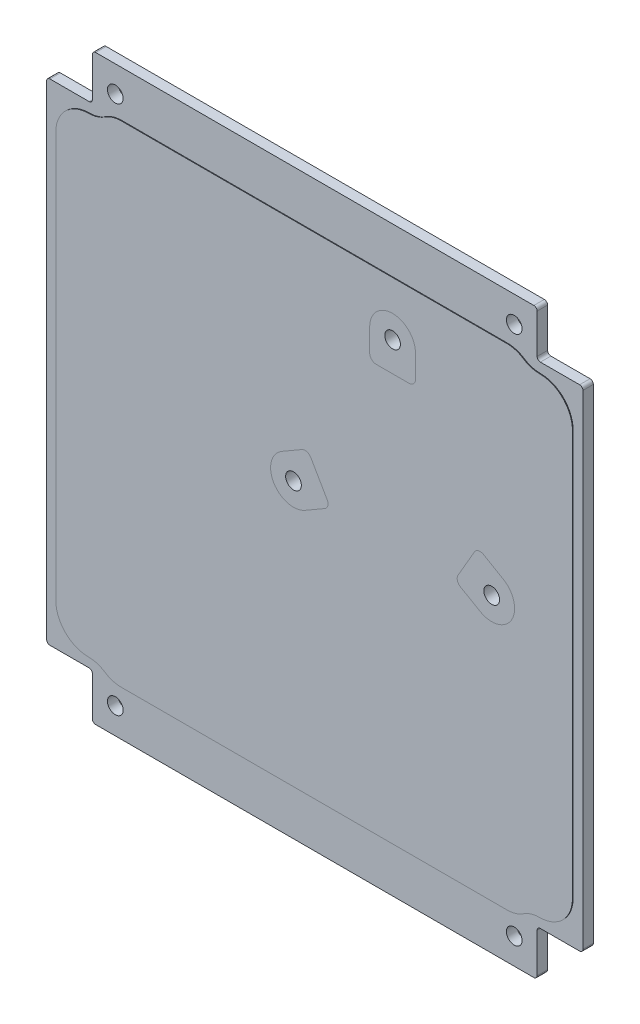
SolidWorks part; units mm, degrees
material "PET"
ref_plane "Front Plane" through (0, 0, 0) normal (0, 0, 1) x (1, 0, 0)
ref_plane "Top Plane" through (0, 0, 0) normal (0, 1, 0) x (1, 0, 0)
ref_plane "Right Plane" through (0, 0, 0) normal (1, 0, 0) x (0, 0, -1)
sketch "Sketch1" plane through (0, 0, 0) normal (0, 0, 1) x (1, 0, 0)
  line L0 (-34, 44) -> (-34, 38)
  line L1 (-33.5, -44.5) -> (33.5, -44.5)
  line L2 (-41, 37) -> (-41, -37)
  line L3 (-33.5, 44.5) -> (33.5, 44.5)
  line L4 (41, -37) -> (41, 37)
  line L5 (34, -44) -> (34, -38)
  line L6 (34.5, -37.5) -> (40.5, -37.5)
  line L7 (-34.5, 37.5) -> (-40.5, 37.5)
  line L8 (34, 44) -> (34, 38)
  line L9 (34.5, 37.5) -> (40.5, 37.5)
  line L10 (-40.5, -37.5) -> (-34.5, -37.5)
  line L11 (-34, -38) -> (-34, -44)
  line L12 (-34.5, -38) -> (34.5, 38) construction
  line L13 (34.5, -38) -> (-34.5, 38) construction
  arc A0 (-33.5, 44.5) -> (-34, 44) centre (-33.5, 44) ccw
  arc A1 (33.5, 44.5) -> (34, 44) centre (33.5, 44) cw
  arc A2 (34, 38) -> (34.5, 37.5) centre (34.5, 38) ccw
  arc A3 (40.5, 37.5) -> (41, 37) centre (40.5, 37) cw
  arc A4 (33.5, -44.5) -> (34, -44) centre (33.5, -44) ccw
  arc A5 (34.5, -37.5) -> (34, -38) centre (34.5, -38) ccw
  arc A6 (40.5, -37.5) -> (41, -37) centre (40.5, -37) ccw
  arc A7 (-34, -44) -> (-33.5, -44.5) centre (-33.5, -44) ccw
  arc A8 (-34, -38) -> (-34.5, -37.5) centre (-34.5, -38) ccw
  arc A9 (-41, -37) -> (-40.5, -37.5) centre (-40.5, -37) ccw
  arc A10 (-40.5, 37.5) -> (-41, 37) centre (-40.5, 37) ccw
  arc A11 (-34.5, 37.5) -> (-34, 38) centre (-34.5, 38) ccw
  point P0 (0, 0)
  dimension "D4" = 0.5
  dimension "D1" = 7
  dimension "D2" = 7
  dimension "D3" = 7
  dimension "D5" = 7
  dimension "D6" = 7
  dimension "D7" = 7
  dimension "D8" = 7
  dimension "D9" = 7
  dimension "D10" = 89
  dimension "D11" = 82
extrude "Boss-Extrude1" add sketch "Sketch1" along normal blind 1.6
sketch "Esboço1" plane through (0, 0, 1.6) normal (0, 0, 1) x (1, 0, 0)
  line L0 (11.8117, 0) -> (-11.978, 0) construction
  line L1 (-29.5, -37.5) -> (29.5, -37.5)
  line L2 (0, 10.1561) -> (0, -5.0161) construction
  line L3 (-29.5, 37.5) -> (29.5, 37.5)
  line L5 (-29.5, -32.5) -> (29.5, 32.5) construction
  line L6 (-29.5, 32.5) -> (29.5, -32.5) construction
  line L8 (-39.5, -31) -> (-39.5, 31)
  line L10 (39.5, -31) -> (39.5, 31)
  line L11 (-39.5, -36) -> (39.5, 36) construction
  line L12 (-39.5, 36) -> (39.5, -36) construction
  arc A0 (-34.5, 36) -> (-32, 36.75) centre (-34.5, 40.5417) ccw
  arc A1 (-29.5, 37.5) -> (-32, 36.75) centre (-29.5, 32.9583) ccw
  arc A2 (-29.5, -37.5) -> (-32, -36.75) centre (-29.5, -32.9583) cw
  arc A3 (-34.5, -36) -> (-32, -36.75) centre (-34.5, -40.5417) cw
  arc A4 (34.5, 36) -> (39.5, 31) centre (34.5, 31) cw
  arc A5 (34.5, -36) -> (39.5, -31) centre (34.5, -31) ccw
  arc A6 (-34.5, -36) -> (-39.5, -31) centre (-34.5, -31) cw
  arc A7 (-39.5, 31) -> (-34.5, 36) centre (-34.5, 31) cw
  arc A8 (29.5, -37.5) -> (32, -36.75) centre (29.5, -32.9583) ccw
  arc A9 (34.5, -36) -> (32, -36.75) centre (34.5, -40.5417) ccw
  arc A10 (29.5, 37.5) -> (32, 36.75) centre (29.5, 32.9583) cw
  arc A11 (34.5, 36) -> (32, 36.75) centre (34.5, 40.5417) cw
  point P0 (0, 0)
  point P1 (0, 0)
  dimension "D2" = 5
  dimension "D3" = 75
  dimension "D5" = 79
extrude "Boss-Extrude2" add sketch "Esboço1" along normal blind 0.1
hole_wizard "M2 Hole1-FixingStructure" positions "Sketch3" profile "Sketch2" hole size "M2" standard "DIN"
sketch "Sketch3" plane through (0, 0, 0) normal (0, 0, -1) x (-1, 0, 0)
  line L0 (-33.5, 44.5) -> (33.5, 44.5) construction
  line L1 (33.5, -44.5) -> (-33.5, -44.5) construction
  line L2 (-41, -37) -> (-41, 37) construction
  line L3 (41, 37) -> (41, -37) construction
  point P0 (-30.5, 40.5)
  point P2 (30.5, 40.5)
  point P4 (-30.5, -40.5)
  point P6 (30.5, -40.5)
  dimension "D1" = 4
  dimension "D2" = 4
  dimension "D3" = 10.5
  dimension "D4" = 10.5
sketch "Sketch2" plane through (30.5, 40.5, 0) normal (1, 0, 0) x (0, 1, 0)
  line L0 (0, 0) -> (0, 200.721)
  line L1 (0, 200.721) -> (1.2, 200)
  line L2 (1.2, 200) -> (1.2, 0)
  line L5 (1.2, 0) -> (0, 0)
  line L10 (0, 200.721) -> (-1.2, 200) construction
  line L11 (0, -6.35) -> (0, 107.95) construction
  dimension "Hole Dia." = 2.4
  dimension "Hole Depth" = 200
  dimension "Drill Angle" = 118
sketch "Sketch4" plane through (0, 0, 1.7) normal (0, 0, 1) x (1, 0, 0)
  circle A0 centre (27.1554, 3) radius 1.2 construction
  circle A1 centre (-3.1554, 3) radius 1.2 construction
  circle A2 centre (12, 29.25) radius 1.2 construction
  circle A3 centre (27.1554, 3) radius 1.2
  circle A4 centre (-3.1554, 3) radius 1.2
  circle A5 centre (12, 29.25) radius 1.2
extrude "Cut-Extrude1" cut sketch "Sketch4" against normal up to surface (1.7 mm away) up to face at (29.3, 40.5, 0)
sketch "Sketch5" plane through (0, 0, 1.7) normal (0, 0, 1) x (1, 0, 0)
  line L4 (1.6256, 1.7189) -> (-1.4054, -0.0311)
  line L5 (26.7404, 7.2811) -> (28.9054, 6.0311)
  line L6 (25.4054, -0.0311) -> (23.2404, 1.2189)
  line L7 (25.8744, 7.7811) -> (28.9054, 6.0311)
  line L8 (25.4054, -0.0311) -> (22.3744, 1.7189)
  line L9 (22.0083, 3.0849) -> (24.5083, 7.4151)
  line L10 (22.0083, 3.0849) -> (24.5083, 7.4151)
  line L11 (-4.9054, 6.0311) -> (-1.8744, 7.7811)
  line L12 (-0.5083, 7.4151) -> (1.9917, 3.0849)
  line L13 (8.5, 25.75) -> (8.5, 29.25)
  line L14 (15.5, 29.25) -> (15.5, 25.75)
  line L15 (14.5, 24.75) -> (9.5, 24.75)
  arc A3 (22.3744, 1.7189) -> (22.0083, 3.0849) centre (22.8744, 2.5849) cw
  arc A4 (25.4054, -0.0311) -> (28.9054, 6.0311) centre (27.1554, 3) ccw
  arc A5 (25.4054, -0.0311) -> (28.9054, 6.0311) centre (27.1554, 3) ccw
  arc A6 (25.8744, 7.7811) -> (24.5083, 7.4151) centre (25.3744, 6.9151) ccw
  circle A7 centre (12, 11.75) radius 4.4 construction
  arc A8 (-1.8744, 7.7811) -> (-0.5083, 7.4151) centre (-1.3744, 6.9151) cw
  arc A9 (-4.9054, 6.0311) -> (-1.4054, -0.0311) centre (-3.1554, 3) ccw
  arc A10 (1.6256, 1.7189) -> (1.9917, 3.0849) centre (1.1256, 2.5849) ccw
  arc A11 (15.5, 25.75) -> (14.5, 24.75) centre (14.5, 25.75) cw
  arc A12 (15.5, 29.25) -> (8.5, 29.25) centre (12, 29.25) ccw
  arc A13 (8.5, 25.75) -> (9.5, 24.75) centre (9.5, 25.75) ccw
  point P13 (12, 11.75)
  point P37 (12, 11.75)
  dimension "D3" = 1
  dimension "D1" = 1
  dimension "D2" = 1
  dimension "D4" = 3
split line "Split Line1"
